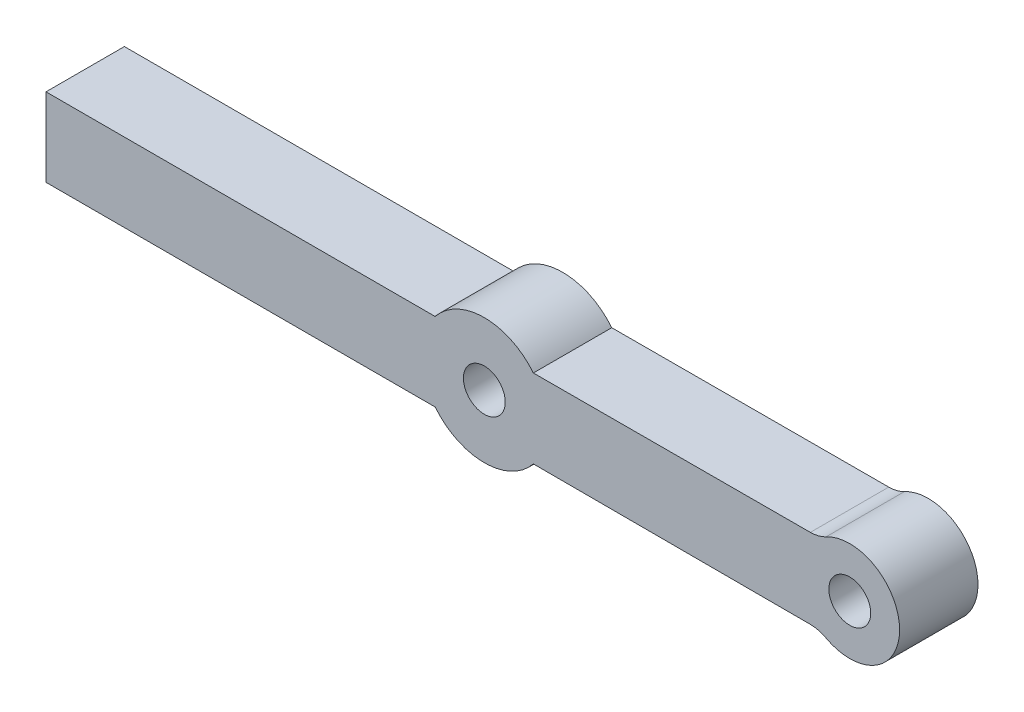
SolidWorks part; units mm, degrees
ref_plane "Front Plane" through (0, 0, 0) normal (0, 0, 1) x (1, 0, 0)
ref_plane "Top Plane" through (0, 0, 0) normal (0, 1, 0) x (1, 0, 0)
ref_plane "Right Plane" through (0, 0, 0) normal (1, 0, 0) x (0, 0, -1)
sketch "Sketch1" plane through (0, 0, 0) normal (0, 0, 1) x (1, 0, 0)
  line L0 (-31.75, 2.9972) -> (-37.7444, 2.9972)
  line L1 (-37.7444, 2.9972) -> (-42.4037, 2.9972)
  line L2 (-31.75, 2.9972) -> (-31.6982, 2.9973)
  line L3 (-61.4537, 2.9972) -> (-61.4537, -2.9972)
  line L4 (-31.75, -2.9972) -> (-31.6982, -2.9973)
  line L5 (-42.4037, 2.9972) -> (-61.4537, 2.9972)
  line L6 (-37.7444, -2.9972) -> (-31.75, -2.9972)
  line L7 (-42.4037, -2.9972) -> (-37.7444, -2.9972)
  line L8 (-61.4537, -2.9972) -> (-55.1037, -2.9972)
  line L9 (-55.1037, -2.9972) -> (-42.4037, -2.9972)
  line L10 (-24.1922, 3.0102) -> (-3.014, 3.0467)
  line L11 (-24.1922, -3.0102) -> (-3.014, -3.0467)
  circle A0 centre (0, 0) radius 1.6
  arc A1 (-1.811, -3.352) -> (-1.811, 3.352) centre (0, 0) ccw
  arc A2 (-1.811, 3.352) -> (-3.014, 3.0467) centre (-3.0184, 5.5867) cw
  arc A3 (-1.811, -3.352) -> (-3.014, -3.0467) centre (-3.0184, -5.5867) ccw
  circle A4 centre (-27.94, 0) radius 1.6
  arc A5 (-31.6982, -2.9973) -> (-24.1922, -3.0102) centre (-27.94, 0) ccw
  arc A6 (-24.1922, 3.0102) -> (-31.6982, 2.9973) centre (-27.94, 0) ccw
  point P17 (-31.75, 0)
  dimension "D1" = 2.54
  dimension "D2" = 2.54
  dimension "D3" = 4.6593
extrude "Boss-Extrude1" add sketch "Sketch1" along normal blind 5.9944
